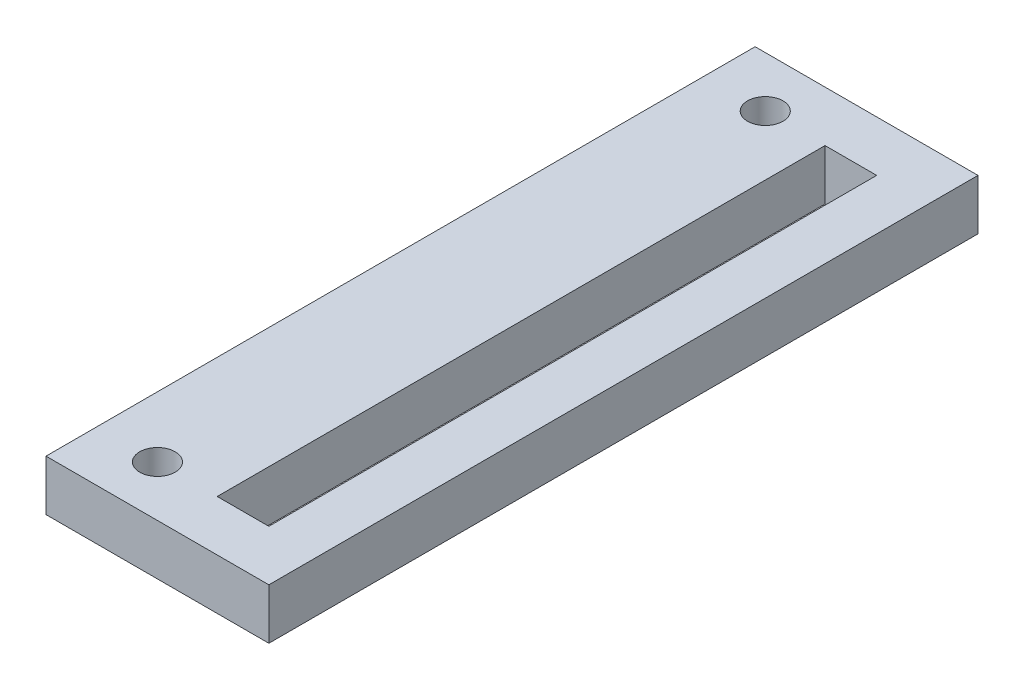
SolidWorks part; units mm, degrees
ref_plane "Front Plane" through (0, 0, 0) normal (0, 0, 1) x (1, 0, 0)
ref_plane "Top Plane" through (0, 0, 0) normal (0, 1, 0) x (1, 0, 0)
ref_plane "Right Plane" through (0, 0, 0) normal (1, 0, 0) x (0, 0, -1)
sketch "Sketch1" plane through (0, 0, 0) normal (0, 1, 0) x (1, 0, 0)
  line L0 (-1000, 35) -> (49000, 35) construction
  line L1 (0, 0) -> (22, 0)
  line L2 (0, 0) -> (0, 70)
  line L3 (0, 70) -> (22, 70)
  line L4 (22, 0) -> (22, 70)
  line L6 (17, 65) -> (11.9, 65)
  line L7 (17, 65) -> (17, 5)
  line L8 (17, 5) -> (11.9, 5)
  line L9 (11.9, 65) -> (11.9, 5)
  circle A0 centre (6, 65) radius 1.75
  circle A1 centre (6, 5) radius 1.75
  point P10 (0, 35)
  point P16 (17, 35)
  dimension "D3" = 3.5
  dimension "D4" = 60
  dimension "D1" = 70
  dimension "D2" = 22
  dimension "D5" = 6
  dimension "D6" = 5.1
  dimension "D7" = 5
  dimension "D8" = 60
extrude "Boss-Extrude1" add sketch "Sketch1" along normal blind 5
